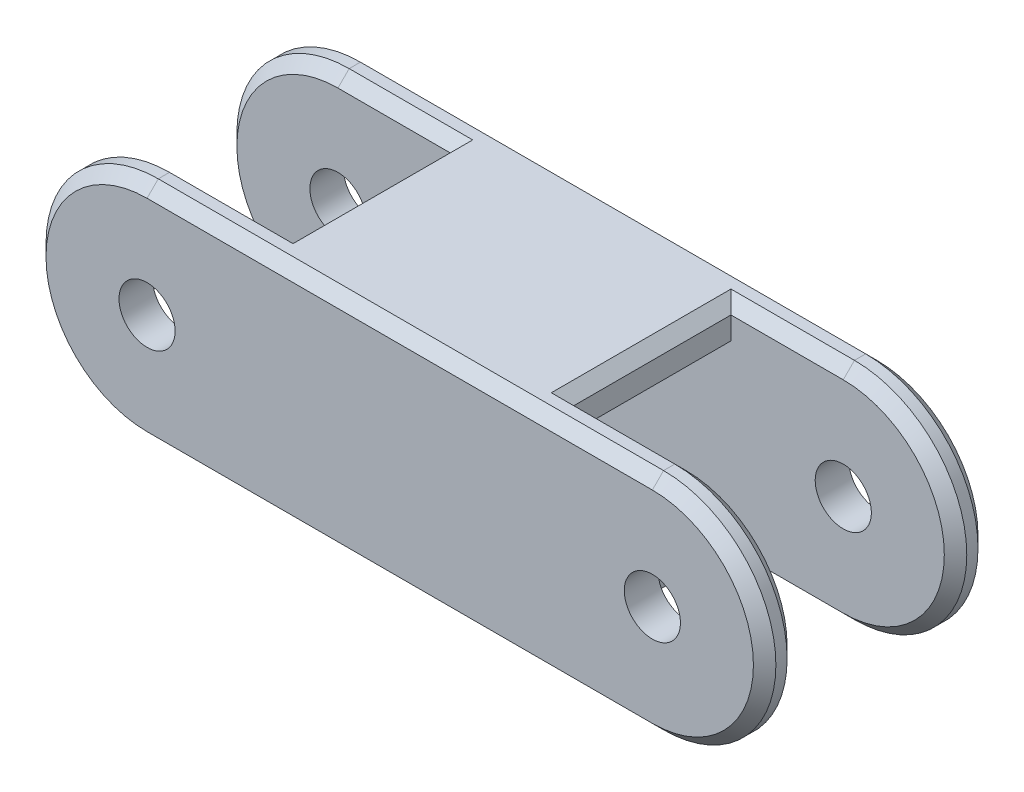
SolidWorks part; units mm, degrees
ref_plane "Front Plane" through (0, 0, 0) normal (0, 0, 1) x (1, 0, 0)
ref_plane "Top Plane" through (0, 0, 0) normal (0, 1, 0) x (1, 0, 0)
ref_plane "Right Plane" through (0, 0, 0) normal (1, 0, 0) x (0, 0, -1)
sketch "Sketch1" plane through (0, 0, 0) normal (0, 0, 1) x (1, 0, 0)
  line L0 (-22.5, 0) -> (22.5, 0) construction
  line L1 (-22.5, 10) -> (22.5, 10)
  line L2 (-22.5, -10) -> (22.5, -10)
  arc A0 (-22.5, 10) -> (-22.5, -10) centre (-22.5, 0) ccw
  arc A1 (22.5, -10) -> (22.5, 10) centre (22.5, 0) ccw
  point P3 (0, 0)
  dimension "D1" = 20
  dimension "D2" = 45
extrude "Boss-Extrude1" add sketch "Sketch1" along normal mid plane 20
sketch "Sketch2" plane through (0, 0, 0) normal (0, 0, 1) x (1, 0, 0)
  line L0 (-22.5, 10) -> (-12.5, 10)
  line L1 (-12.5, 10) -> (-12.5, -10)
  line L2 (-12.5, -10) -> (-22.5, -10)
  line L3 (0, 10) -> (0, -10) construction
  line L4 (12.5, -10) -> (22.5, -10)
  line L5 (12.5, 10) -> (12.5, -10)
  line L6 (22.5, 10) -> (12.5, 10)
  arc A0 (-22.5, 10) -> (-22.5, -10) centre (-22.5, 0) ccw
  arc A1 (22.5, 10) -> (22.5, -10) centre (22.5, 0) cw
  dimension "D1" = 20
extrude "Cut-Extrude1" cut sketch "Sketch2" against normal mid plane 14
sketch "Sketch3" plane through (0, 0, 0) normal (0, 0, 1) x (1, 0, 0)
  line L0 (0, 10) -> (0, -10) construction
  line L1 (22.5, 10) -> (-22.5, 10) construction
  line L2 (-22.5, -10) -> (22.5, -10) construction
  circle A0 centre (-22.5, 0) radius 2.5
  circle A1 centre (22.5, 0) radius 2.5
  dimension "D1" = 5
extrude "Cut-Extrude2" cut sketch "Sketch3" against normal mid plane 20
chamfer "Chamfer2" distance 1 angle 45 12 edges at (17.5, -10, -7) (32.5, 0, -7) (17.5, 10, -7) (17.5, -10, 7) (32.5, 0, 7) (17.5, 10, 7) (-17.5, -10, 7) (-32.5, 0, 7) (-17.5, 10, 7) (-17.5, -10, -7) (-32.5, 0, -7) (-17.5, 10, -7)
chamfer "Chamfer3" distance 1 angle 45 8 edges at (0, -10, -10) (32.5, 0, -10) (-32.5, 0, -10) (0, 10, -10) (0, -10, 10) (32.5, 0, 10) (-32.5, 0, 10) (0, 10, 10)
shell "Shell1" thickness 3 removed face at (12.5, 0, 0) removed face at (-12.5, 0, 0)
chamfer "Chamfer4" distance 1 angle 45 4 edges at (12.5, -10, 0) (12.5, 10, 0) (-12.5, -10, 0) (-12.5, 10, 0)
